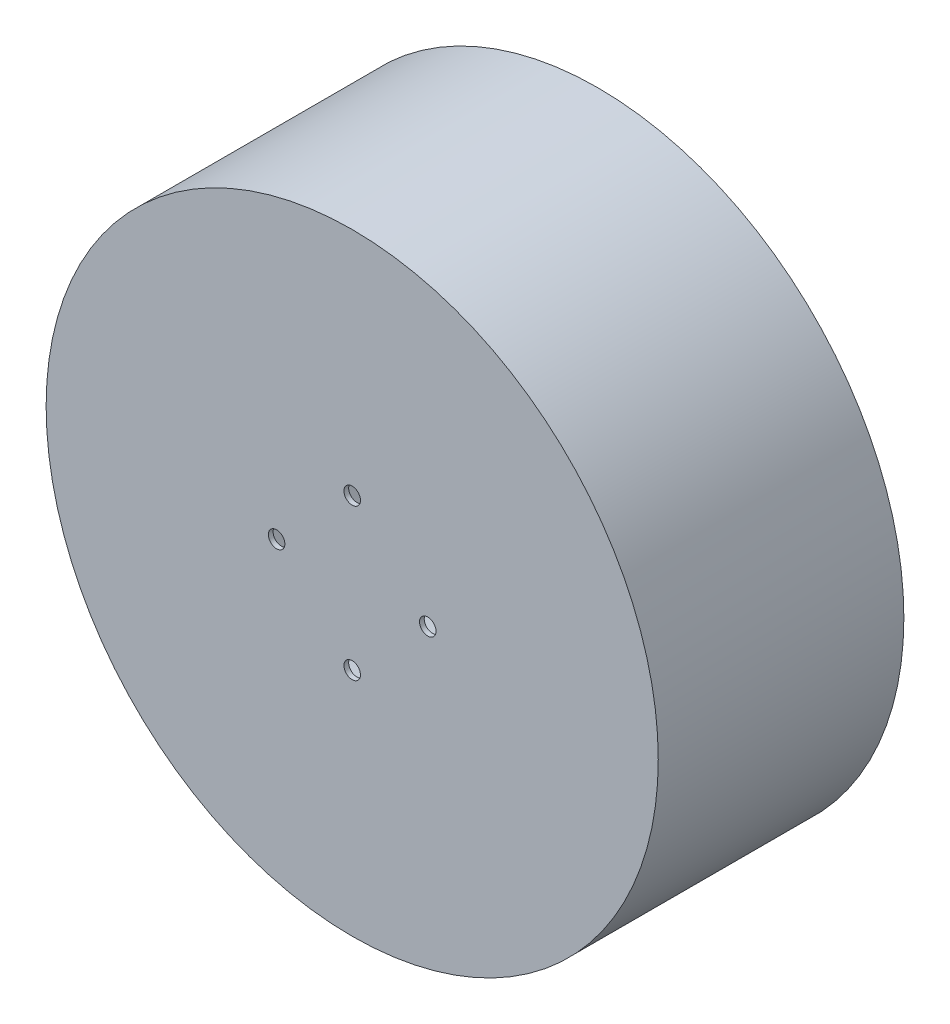
SolidWorks part; units mm, degrees
ref_plane "Front Plane" through (0, 0, 0) normal (0, 0, 1) x (1, 0, 0)
ref_plane "Top Plane" through (0, 0, 0) normal (0, 1, 0) x (1, 0, 0)
ref_plane "Right Plane" through (0, 0, 0) normal (1, 0, 0) x (0, 0, -1)
sketch "Sketch1" plane through (0, 0, 0) normal (0, 0, 1) x (1, 0, 0)
  circle A2 centre (0, 50.8) radius 5.5563
  circle A3 centre (50.8, 0) radius 5.5562
  circle A4 centre (0, -50.8) radius 5.5563
  circle A5 centre (-50.8, 0) radius 5.5563
  circle A6 centre (0, 0) radius 101.6
  point P15 (0, 0)
  dimension "D2" = 50.8
  dimension "D3" = 11.1125
  dimension "D5" = 203.2
  dimension "D4" = 4
extrude "Boss-Extrude2" add sketch "Sketch1" along normal blind 3.175
sketch "Sketch2" plane through (0, 0, 3.175) normal (0, 0, 1) x (1, 0, 0)
  circle A0 centre (0, 0) radius 205.74
  circle A1 centre (0, 0) radius 101.6
  dimension "D1" = 411.48
  dimension "D2" = 203.2
extrude "Boss-Extrude3" add sketch "Sketch2" against normal blind 165.1
